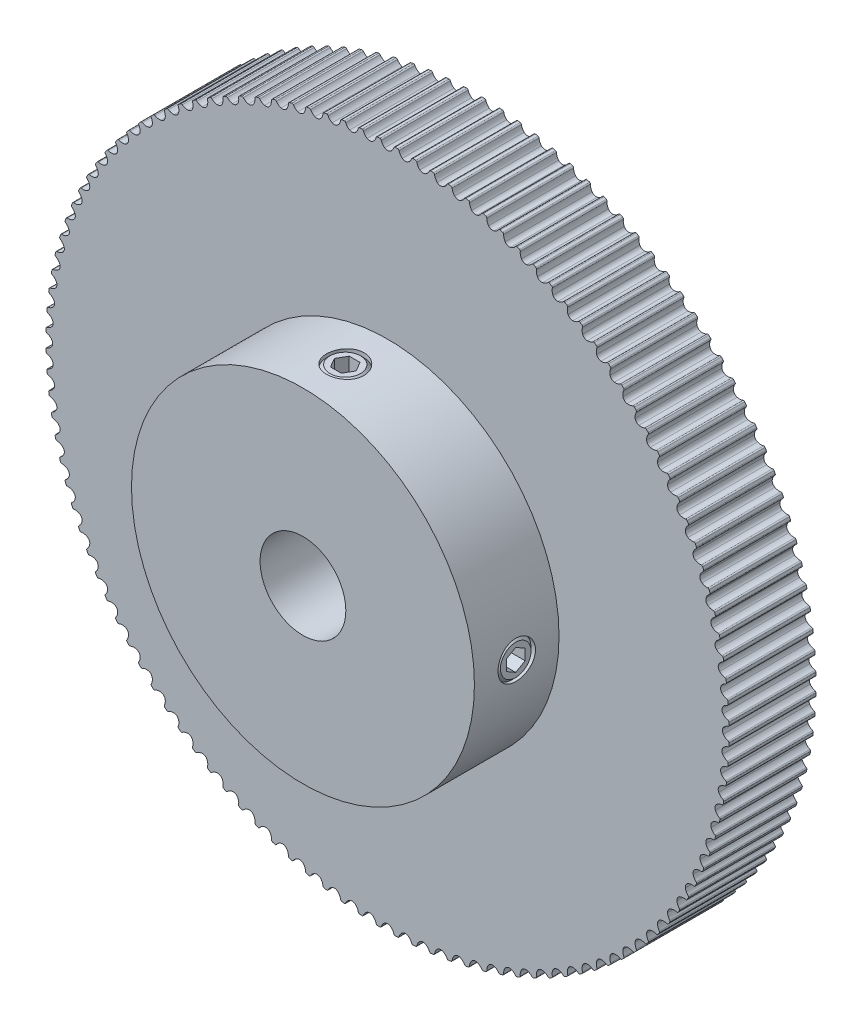
SolidWorks part; units mm, degrees
ref_plane "Front Plane" through (0, 0, 0) normal (0, 0, 1) x (1, 0, 0)
ref_plane "Top Plane" through (0, 0, 0) normal (0, 1, 0) x (1, 0, 0)
ref_plane "Right Plane" through (0, 0, 0) normal (1, 0, 0) x (0, 0, -1)
sketch "Sketch1" plane through (0, 0, 0) normal (0, 0, 1) x (1, 0, 0)
  line L3 (0, 37.9476) -> (1.9993, 37.8949) construction
  line L4 (0, 0) -> (0, 37.1976) construction
  line L5 (0, 37.1976) -> (0, 38.479) construction
  line L15 (1.9993, 37.8949) -> (2.0301, 38.479)
  line L16 (2.0301, 38.479) -> (-2.0301, 38.479)
  line L17 (0, 37.1976) -> (0.1538, 37.1976) construction
  line L18 (-1.9993, 37.8949) -> (-2.0301, 38.479)
  circle A0 centre (0, 0) radius 38.2015 construction
  circle A1 centre (0, 0) radius 37.9476 construction
  circle A2 centre (0, 0) radius 37.6936 construction
  arc A10 (0.851, 37.9381) -> (1.9993, 37.8949) centre (0, 0) cw
  arc A11 (-0.3168, 37.2969) -> (0.3168, 37.2969) centre (0, 37.7526) ccw
  arc A12 (0.3168, 37.2969) -> (0.704, 37.8311) centre (-0.254, 38.118) ccw
  arc A13 (0.704, 37.8311) -> (0.851, 37.9381) centre (0.8477, 37.7881) cw
  arc A14 (-0.851, 37.9381) -> (-1.9993, 37.8949) centre (0, 0) ccw
  arc A15 (-0.704, 37.8311) -> (-0.851, 37.9381) centre (-0.8477, 37.7881) ccw
  arc A16 (-0.3168, 37.2969) -> (-0.704, 37.8311) centre (0.254, 38.118) cw
  point P11 (0, 38.2015)
  point P13 (0, 37.9476)
  point P14 (0, 37.6936)
  dimension "D2" = 0.2775
sketch "Sketch2" plane through (0, 0, 0) normal (1, 0, 0) x (0, 0, -1)
  line L0 (-9.525, 4.7625) -> (9.525, 4.7625)
  line L1 (-9.525, 4.7625) -> (-9.525, 19.05)
  line L2 (-9.525, 19.05) -> (-0.125, 19.05)
  line L3 (-0.125, 19.05) -> (-0.125, 37.9476)
  line L9 (9.525, 37.9476) -> (9.525, 4.7625)
  line L10 (-9.525, 0) -> (9.525, 0) construction
  line L16 (-0.125, 37.9476) -> (9.525, 37.9476)
  point P25 (9.525, 0)
  point P26 (-0.125, 0)
  dimension "OA" = 19.05
  dimension "Bore" = 9.525
  dimension "Hub Dia" = 38.1
  dimension "Outside Width" = 9.65
revolve "Revolve1" add sketch "Sketch2" angle 360 mid plane about L10
sketch "Sketch3" plane through (0, 0, 0) normal (0, 0, 1) x (1, 0, 0)
  line L3 (1.9993, 37.8949) -> (2.0301, 38.479) construction
  line L4 (-1.9993, 37.8949) -> (-2.0301, 38.479) construction
  line L5 (2.0301, 38.479) -> (-2.0301, 38.479) construction
  line L6 (1.9993, 37.8949) -> (2.0301, 38.479)
  line L7 (-1.9993, 37.8949) -> (-2.0301, 38.479)
  line L8 (2.0301, 38.479) -> (-2.0301, 38.479)
  arc A0 (1.9993, 37.8949) -> (0.851, 37.9381) centre (0, 0) ccw construction
  arc A1 (0.851, 37.9381) -> (0.704, 37.8311) centre (0.8477, 37.7881) ccw construction
  arc A3 (0.3168, 37.2969) -> (0.704, 37.8311) centre (-0.254, 38.118) ccw construction
  arc A4 (-0.3168, 37.2969) -> (0.3168, 37.2969) centre (0, 37.7526) ccw construction
  arc A5 (-0.704, 37.8311) -> (-0.3168, 37.2969) centre (0.254, 38.118) ccw construction
  arc A6 (-0.704, 37.8311) -> (-0.851, 37.9381) centre (-0.8477, 37.7881) ccw construction
  arc A7 (-0.851, 37.9381) -> (-1.9993, 37.8949) centre (0, 0) ccw construction
  arc A8 (1.9993, 37.8949) -> (0.851, 37.9381) centre (0, 0) ccw
  arc A9 (0.851, 37.9381) -> (0.704, 37.8311) centre (0.8477, 37.7881) ccw
  arc A10 (0.3168, 37.2969) -> (0.704, 37.8311) centre (-0.254, 38.118) ccw
  arc A11 (-0.3168, 37.2969) -> (0.3168, 37.2969) centre (0, 37.7526) ccw
  arc A12 (-0.704, 37.8311) -> (-0.3168, 37.2969) centre (0.254, 38.118) ccw
  arc A13 (-0.704, 37.8311) -> (-0.851, 37.9381) centre (-0.8477, 37.7881) ccw
  arc A14 (-0.851, 37.9381) -> (-1.9993, 37.8949) centre (0, 0) ccw
extrude "Cut-Extrude1" cut sketch "Sketch3" against normal through all from surface starting at face at (19.05, 0, 0.125)
pattern_circular "CirPattern1" count 120 over 360 about axis through (0, 0, 9.525) along (0, 0, 1) of "Cut-Extrude1"
sketch "Sketch4" plane through (0, 0, 0) normal (1, 0, 0) x (0, 0, -1)
  line L0 (-9.525, 0) -> (-0.125, 0) construction
  line L1 (-9.525, 19.05) -> (-9.525, -19.05) construction
  line L2 (-0.125, 19.05) -> (-0.125, -19.05) construction
  circle A0 centre (-4.825, 0) radius 2.0828
  dimension "D1" = 4.1656
extrude "Cut-Extrude2" cut sketch "Sketch4" along normal through all
ref_plane "Plane1" through (0, 0, 4.825) normal (0, 0, 1) x (1, 0, 0)
sketch "Sketch5" plane through (0, 0, 4.825) normal (0, 0, 1) x (1, 0, 0)
  line L0 (4.2829, -2.0828) -> (18.9358, -2.0828) construction
  line L1 (5.1435, -2.0828) -> (18.5548, -2.0828)
  line L2 (18.9358, -1.7018) -> (18.9358, 0)
  line L3 (18.9358, 0) -> (4.7625, 0) construction
  line L4 (4.7625, -1.7018) -> (4.7625, 0)
  line L5 (5.1435, -2.0828) -> (4.7625, -1.7018)
  line L6 (18.5548, -2.0828) -> (18.9358, -1.7018)
  line L13 (4.2829, -2.0828) -> (18.9358, -2.0828) construction
  line L23 (4.7625, 0) -> (18.9358, 0)
  circle A0 centre (0, 0) radius 19.05 construction
  circle A1 centre (0, 0) radius 4.7625 construction
  point P0 (4.7625, -2.0828)
  point P3 (18.9358, -2.0828)
  point P4 (-19.05, 0)
  point P6 (-4.7625, 0)
revolve "Revolve2" add sketch "Sketch5" angle 360 mid plane about L3
sketch "Sketch6" plane through (18.9358, 0, 0) normal (1, 0, 0) x (0, 0, -1)
  line L1 (-4.825, 1.2025) -> (-5.8664, 0.6013)
  line L2 (-5.8664, 0.6013) -> (-5.8664, -0.6013)
  line L3 (-5.8664, -0.6013) -> (-4.825, -1.2025)
  line L4 (-4.825, -1.2025) -> (-3.7836, -0.6013)
  line L5 (-3.7836, -0.6013) -> (-3.7836, 0.6013)
  line L6 (-3.7836, 0.6013) -> (-4.825, 1.2025)
  circle A0 centre (-4.825, 0) radius 1.0414 construction
  dimension "D1" = 2.0828
extrude "Cut-Extrude3" cut sketch "Sketch6" against normal blind 1.524
pattern_circular "CirPattern2" count 2 over 90 about axis through (0, 0, 9.525) along (0, 0, 1) of "Cut-Extrude2", "Revolve2", "Cut-Extrude3"
ref_axis "Center Axis 1" through (0, 0, -9.525) along (0, 0, 1)
ref_plane "Contact Plane 1" through (0, 0, 9.525) normal (0, 0, 1) x (1, 0, 0)
ref_plane "Contact Plane 2" through (0, 0, -9.525) normal (0, 0, -1) x (-1, 0, 0)
equation "\"D2@Sketch1\" = \"R3@Sketch1\"/2"
equation "\"D1@Sketch6\" = \"D1@Sketch4\"/2"
